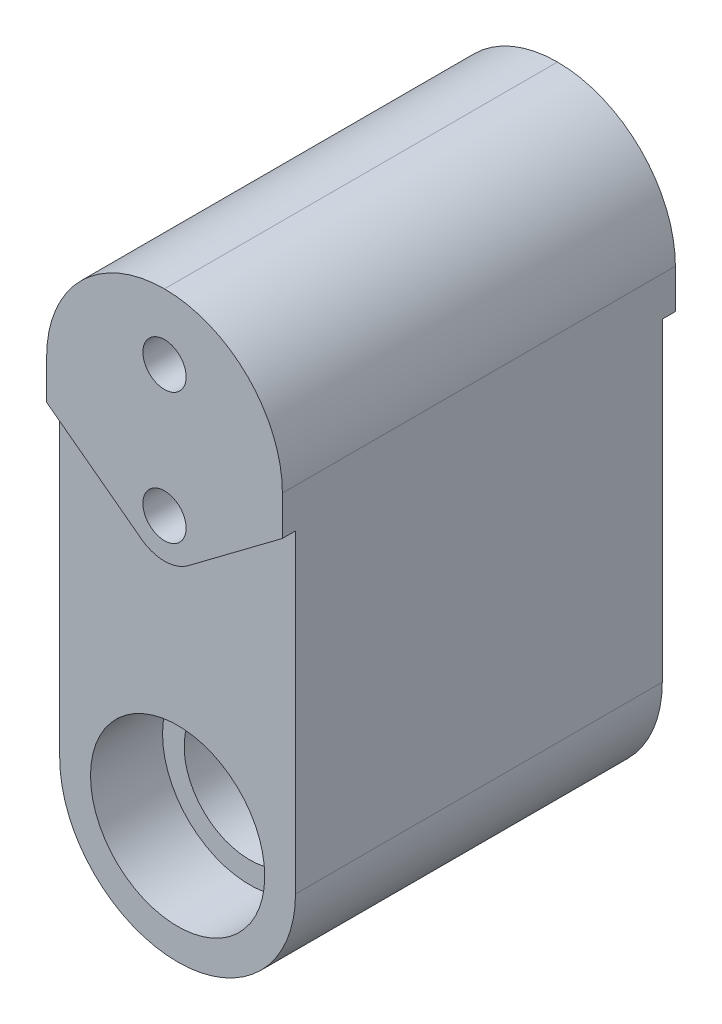
SolidWorks part; units mm, degrees
ref_plane "Спереди" through (0, 0, 0) normal (0, 0, 1) x (1, 0, 0)
ref_plane "Сверху" through (0, 0, 0) normal (0, 1, 0) x (1, 0, 0)
ref_plane "Справа" through (0, 0, 0) normal (1, 0, 0) x (0, 0, -1)
sketch "Эскиз1" plane through (0, 0, 0) normal (0, 0, 1) x (1, 0, 0)
  line L0 (0, 36) -> (0, -9) construction
  line L1 (-9, 36) -> (9, 36)
  line L2 (-9, 36) -> (-9, -9)
  line L3 (-9, -9) -> (9, -9)
  line L4 (9, 36) -> (9, -9)
  line L6 (-9, 0) -> (9, 0) construction
  dimension "D1" = 18
  dimension "D2" = 9
  dimension "D3" = 36
extrude "тело" add sketch "Эскиз1" along normal blind 14 and the other way blind 14
sketch "Эскиз2" plane through (0, 0, 14) normal (0, 0, 1) x (1, 0, 0)
  circle A0 centre (0, 0) radius 6.65
  dimension "D1" = 13.3
extrude "углубление для подшипника" cut sketch "Эскиз2" against normal blind 5.5
mirror "Зеркальное отражение2" about plane through (0, 0, 0) normal (0, 0, 1) of "углубление для подшипника"
sketch "Эскиз4" plane through (0, 0, 8.5) normal (0, 0, 1) x (1, 0, 0)
  circle A0 centre (0, 0) radius 5
  dimension "D1" = 10
extrude "сквозное отверстие" cut sketch "Эскиз4" against normal through all
sketch "Эскиз5" plane through (0, 0, -14) normal (0, 0, -1) x (-1, 0, 0)
  line L0 (0, 36) -> (0, -9) construction
  line L1 (-9, 36) -> (9, 36) construction
  line L2 (9, -9) -> (-9, -9) construction
  circle A0 centre (0, 31) radius 1.65
  circle A1 centre (0, 21) radius 1.65
  dimension "D1" = 3.3
  dimension "D2" = 10
  dimension "D3" = 5
extrude "отверстия под болты" cut sketch "Эскиз5" against normal through all
fillet "Скругление1" radius 9 2 edges at (9, -9, 0) (-9, -9, 0)
sketch "Эскиз9" plane through (0, 0, 14) normal (0, 0, 1) x (1, 0, 0)
  line L0 (-9, 36) -> (-9, 24)
  line L1 (-9, 36) -> (-9, 0) construction
  line L2 (-9, 36) -> (9, 36)
  line L3 (-9, 24) -> (-1.9948, 18.7593)
  line L4 (9, 36) -> (9, 24)
  line L5 (9, 24) -> (1.8, 18.6)
  line L6 (9, 0) -> (9, 36) construction
  arc A0 (-1.9948, 18.7593) -> (1.8, 18.6) centre (0, 21) ccw
  circle A1 centre (0, 21) radius 1.65
  circle A2 centre (0, 31) radius 1.65
  circle A3 centre (0, 31) radius 1.65 construction
  circle A4 centre (0, 21) radius 1.65 construction
  dimension "D1" = 6
  dimension "D2" = 12
extrude "выступы" add sketch "Эскиз9" along normal blind 1
mirror "Зеркальное отражение1" about plane through (0, 0, 0) normal (0, 0, 1) of "выступы"
fillet "Скругление2" radius 9 2 edges at (9, 36, 0) (-9, 36, 0)
